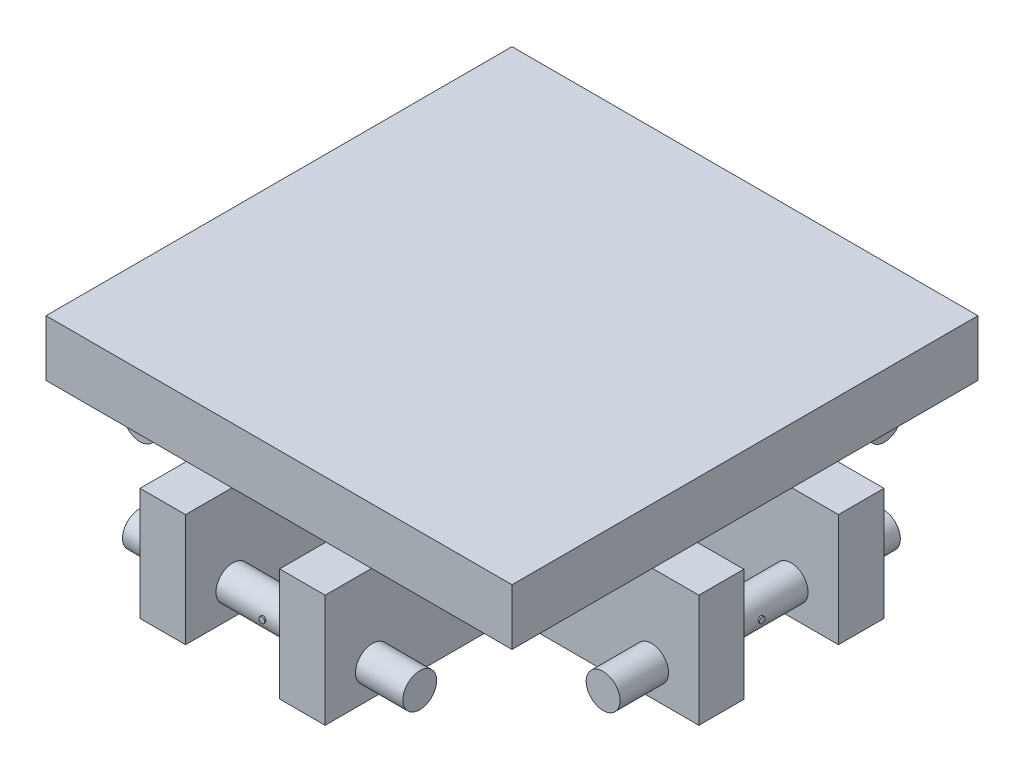
SolidWorks part; units mm, degrees
ref_plane "Front Plane" through (0, 0, 0) normal (0, 0, 1) x (1, 0, 0)
ref_plane "Top Plane" through (0, 0, 0) normal (0, 1, 0) x (1, 0, 0)
ref_plane "Right Plane" through (0, 0, 0) normal (1, 0, 0) x (0, 0, -1)
sketch "Sketch1" plane through (0, 0, 0) normal (0, 1, 0) x (1, 0, 0)
  line L1 (-40.432, 34.9347) -> (39.368, 34.9347)
  line L2 (-40.432, 34.9347) -> (-40.432, -44.8653)
  line L3 (-40.432, -44.8653) -> (39.368, -44.8653)
  line L4 (39.368, 34.9347) -> (39.368, -44.8653)
  dimension "D1" = 79.8
  dimension "D2" = 79.8
extrude "Boss-Extrude1" add sketch "Sketch1" along normal blind 9.6 contours L4 L3 L2 L1
sketch "Sketch3" plane through (0, 0, 0) normal (0, -1, 0) x (1, 0, 0)
  line L0 (-46.5398, 20.8153) -> (47.318, 20.8153)
  line L1 (-16.382, 20.8153) -> (15.318, 20.8153)
  line L2 (-16.382, 20.8153) -> (-16.382, -10.8847)
  line L3 (-16.382, -10.8847) -> (15.318, -10.8847)
  line L4 (15.318, 20.8153) -> (15.318, -10.8847)
  line L9 (-48.382, -3.0847) -> (47.318, -3.0847)
  line L10 (-48.382, -3.0847) -> (-48.382, -10.8847)
  line L11 (-48.382, -10.8847) -> (47.318, -10.8847)
  line L12 (47.318, -3.0847) -> (47.318, -10.8847)
  line L13 (-46.5398, 20.8153) -> (-46.5398, 13.1153)
  line L14 (-46.5398, 13.1153) -> (47.318, 13.1153)
  line L15 (47.318, 20.8153) -> (47.318, 13.1153)
  line L24 (39.368, -34.9347) -> (39.368, 44.8653) construction
  line L25 (-40.432, -34.9347) -> (39.368, -34.9347) construction
  line L26 (7.518, 25.419) -> (7.518, -6.281)
  line L27 (-16.382, 52.8153) -> (-8.582, 52.8153)
  line L28 (-16.382, 52.8153) -> (-16.382, -42.8847)
  line L29 (-16.382, -42.8847) -> (-8.582, -42.8847)
  line L30 (-8.582, 52.8153) -> (-8.582, -42.8847)
  line L31 (7.518, 52.8153) -> (15.318, 52.8153)
  line L32 (7.518, 52.8153) -> (7.518, -42.8847)
  line L33 (7.518, -42.8847) -> (15.318, -42.8847)
  line L34 (15.318, 52.8153) -> (15.318, -42.8847)
  dimension "D1" = 31.7
  dimension "D2" = 31.7
  dimension "D3" = 95.7
  dimension "D4" = 7.8
  dimension "D5" = 32
  dimension "D6" = 95.7
  dimension "D7" = 32
  dimension "D8" = 95.7
  dimension "D9" = 16.2
  dimension "D10" = 7.8
  dimension "D11" = 7.8
  dimension "D12" = 32
  dimension "D13" = 24.05
  dimension "D14" = 24.05
extrude "Boss-Extrude2" add sketch "Sketch3" along normal blind 19.3 contours L1 L26 L14 L4 | L1 L30 L14 L26 | L14 L30 L9 L26 | L30 L0 L2 L14 | L11 L14 L2 L0 | L30 L12 L28 L0 | L34 L12 L32 L1 | L34 L31 L32 L12 | L30 L27 L28 L12 | L13 L14 L11 L0 | L15 L0 L9 L14 | L4 L14 L9 L0 | L14 L26 L9 L4 | L30 L14 L2 L9 | L30 L9 L2 L3 | L11 L2 L9 | L10 L11 L9 | L9 L30 L11 L26 | L9 L26 L11 L4 | L34 L11 L32 L10 | L4 L11 L9 | L12 L9 L11 | L34 L10 L32 L33 | L30 L3 L28 L10 | L30 L10 L28 L29 region at (-31.4609, 0, 16.9653) region at (-12.482, 0, 36.8153) region at (-12.482, 0, 16.9653) region at (-0.532, 0, 16.9653) region at (-12.482, 0, 5.0153) region at (11.418, 0, 36.8153) region at (11.418, 0, 16.9653) region at (-0.532, 0, 5.0153) region at (-12.482, 0, -6.9847) region at (-32.382, 0, -6.9847) region at (31.318, 0, 16.9653) region at (11.418, 0, 5.0153) region at (-0.532, 0, -6.9847) region at (-12.482, 0, -26.8847) region at (11.418, 0, -6.9847) region at (31.318, 0, -6.9847) region at (11.418, 0, -26.8847)
sketch "Sketch4" plane through (0, 0, -3.0847) normal (0, 0, 1) x (1, 0, 0)
  line L0 (-48.382, -19.3) -> (-48.382, 0) construction
  line L1 (-48.382, -19.3) -> (-16.382, -19.3) construction
  circle A0 centre (-40.282, -14.1) radius 2.9
  dimension "D1" = 8.1
  dimension "D2" = 5.8
  dimension "D3" = 5.2
extrude "Boss-Extrude3" add sketch "Sketch4" along normal blind 32 and the other way blind 16
sketch "Sketch5" plane through (-8.582, 0, 0) normal (1, 0, 0) x (0, 0, -1)
  line L0 (-52.8153, -19.3) -> (-20.8153, -19.3) construction
  line L1 (-52.8153, -19.3) -> (-52.8153, 0) construction
  circle A0 centre (-44.7153, -14.1) radius 2.9
  dimension "D2" = 5.8
  dimension "D1" = 5.2
  dimension "D3" = 8.1
extrude "Boss-Extrude4" add sketch "Sketch5" along normal blind 32 and the other way blind 16
sketch "Sketch6" plane through (0, 0, 13.1153) normal (0, 0, -1) x (-1, 0, 0)
  line L0 (-47.318, -19.3) -> (-47.318, 0) construction
  line L1 (-15.318, -19.3) -> (-47.318, -19.3) construction
  circle A0 centre (-39.218, -14.1) radius 2.9
  dimension "D1" = 5.8
  dimension "D2" = 8.1
  dimension "D3" = 5.2
extrude "Boss-Extrude5" add sketch "Sketch6" along normal blind 32 and the other way blind 16
sketch "Sketch7" plane through (7.518, 0, 0) normal (-1, 0, 0) x (0, 0, 1)
  line L0 (-10.8847, -19.3) -> (-42.8847, -19.3) construction
  line L2 (-42.8847, -19.3) -> (-42.8847, 0) construction
  circle A0 centre (-34.7847, -14.1) radius 2.9
  dimension "D1" = 5.8
  dimension "D2" = 5.2
  dimension "D3" = 8.1
extrude "Boss-Extrude6" add sketch "Sketch7" along normal blind 32 and the other way blind 16
sketch "Sketch8" plane through (0, 0, 20.8153) normal (0, 0, 1) x (1, 0, 0)
  line L0 (-8.582, -19.3) -> (-8.582, 0) construction
  line L1 (7.518, -19.3) -> (7.518, 0) construction
  line L3 (-8.582, -19.3) -> (7.518, -19.3) construction
  circle A0 centre (-0.532, -14.1) radius 0.5
  dimension "D1" = 1
  dimension "D2" = 8.05
  dimension "D3" = 8.05
  dimension "D4" = 5.2
extrude "Boss-Extrude7" add sketch "Sketch8" along normal blind 27.0075
sketch "Sketch10" plane through (-16.382, 0, 0) normal (-1, 0, 0) x (0, 0, 1)
  line L0 (13.1153, -19.3) -> (-3.0847, -19.3) construction
  line L1 (-3.0847, -19.3) -> (-3.0847, 0) construction
  circle A0 centre (4.9653, -14.1) radius 0.5
  dimension "D1" = 1
  dimension "D2" = 5.2
  dimension "D3" = 8.05
extrude "Boss-Extrude9" add sketch "Sketch10" along normal blind 27.01
sketch "Sketch11" plane through (15.318, 0, 0) normal (1, 0, 0) x (0, 0, -1)
  line L0 (3.0847, -19.3) -> (3.0847, 0) construction
  line L1 (-13.1153, -19.3) -> (3.0847, -19.3) construction
  circle A0 centre (-4.9653, -14.1) radius 0.5
  dimension "D2" = 1
  dimension "D3" = 5.2
  dimension "D1" = 8.05
extrude "Boss-Extrude10" add sketch "Sketch11" along normal blind 27.01
sketch "Sketch13" plane through (0, 0, -10.8847) normal (0, 0, -1) x (-1, 0, 0)
  line L0 (8.582, -19.3) -> (-7.518, -19.3) construction
  line L1 (-7.518, -19.3) -> (-7.518, 0) construction
  circle A0 centre (0.532, -14.1) radius 0.5
  dimension "D3" = 1
  dimension "D1" = 5.2
  dimension "D2" = 8.05
extrude "Boss-Extrude11" add sketch "Sketch13" along normal blind 27.01
